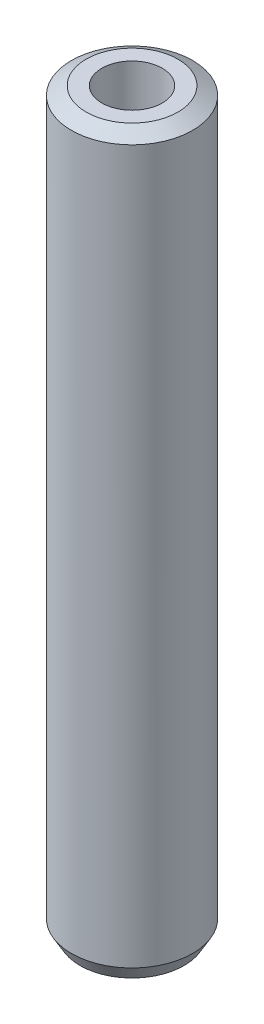
SolidWorks part; units mm, degrees
ref_plane "Front Plane" through (0, 0, 0) normal (0, 0, 1) x (1, 0, 0)
ref_plane "Top Plane" through (0, 0, 0) normal (0, 1, 0) x (1, 0, 0)
ref_plane "Right Plane" through (0, 0, 0) normal (1, 0, 0) x (0, 0, -1)
sketch "Sketch1" plane through (0, 0, 0) normal (0, 1, 0) x (1, 0, 0)
  circle A0 centre (0, 0) radius 17.5
  dimension "SHAFT_OD" = 35
extrude "Boss-Extrude1" add sketch "Sketch1" along normal blind 212.5979
sketch "Sketch2" plane through (0, 0, 0) normal (0, 1, 0) x (1, 0, 0)
  circle A0 centre (0, 0) radius 8.721
  dimension "BORE_D" = 17.4421
extrude "Cut-Extrude1" cut sketch "Sketch2" along normal through all
chamfer "Chamfer1" distance 2.45 angle 60 2 edges at (0, 212.5979, 17.5) (0, 0, 17.5) first distance on face at (0, 212.5979, 17.5) first distance on face at (0, 0, 8.721)
